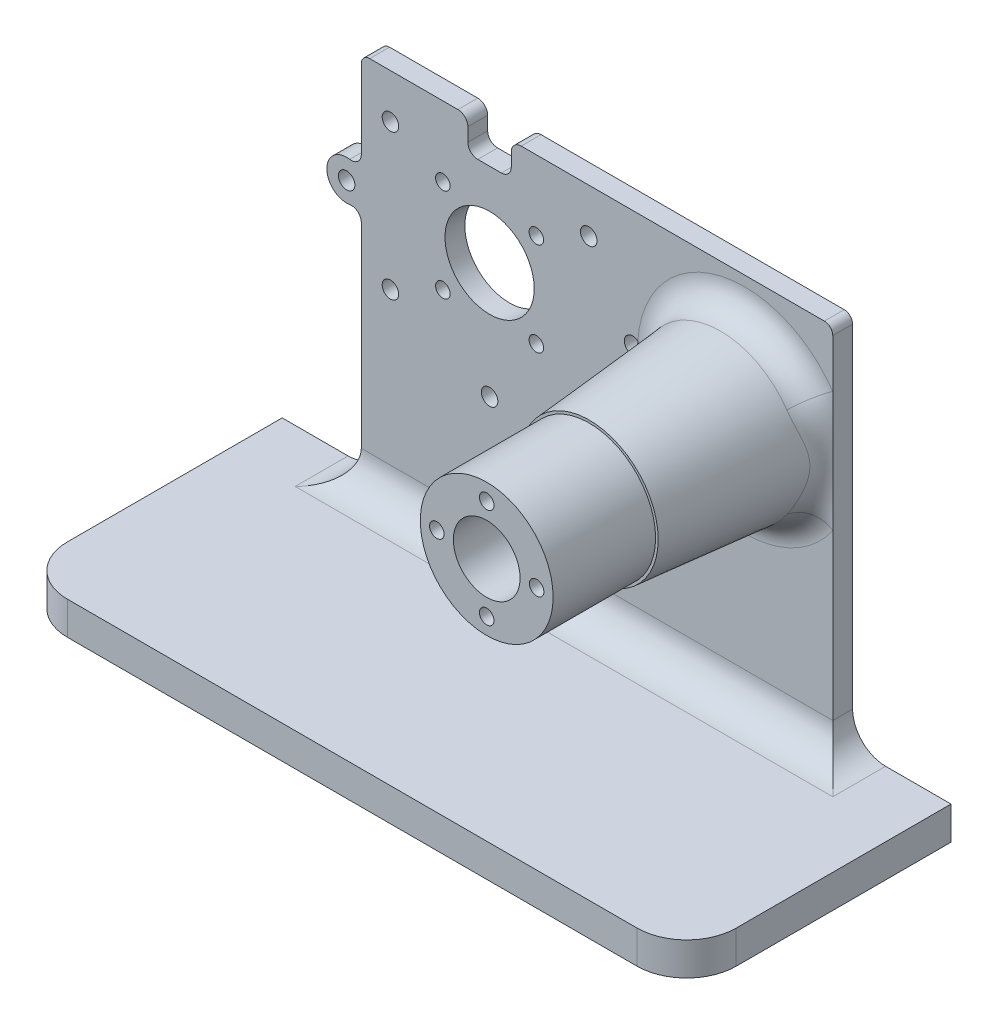
SolidWorks part; units mm, degrees
ref_plane "Front Plane" through (0, 0, 0) normal (0, 0, 1) x (1, 0, 0)
ref_plane "Top Plane" through (0, 0, 0) normal (0, 1, 0) x (1, 0, 0)
ref_plane "Right Plane" through (0, 0, 0) normal (1, 0, 0) x (0, 0, -1)
sketch "Sketch1" plane through (0, 0, 0) normal (0, 0, 1) x (1, 0, 0)
  line L1 (-36.2849, 35.3895) -> (-9.5777, 35.3895)
  line L2 (-38.8249, 32.8495) -> (-38.8249, 8.9302)
  line L3 (-38.8249, -78) -> (103.8382, -78)
  line L4 (103.8382, 32.8495) -> (103.8382, -78)
  line L5 (-38.8249, -8.8387) -> (-38.8249, -78)
  line L6 (0, -55) -> (0, 55) construction
  line L7 (9.5548, 35.3895) -> (101.2982, 35.3895)
  line L9 (-6.5777, 32.3895) -> (-6.5777, 28.3344)
  line L10 (-3.5777, 25.3344) -> (3.5548, 25.3344)
  line L11 (6.5548, 32.3895) -> (6.5548, 28.3344)
  arc A0 (101.2982, 35.3895) -> (103.8382, 32.8495) centre (101.2982, 32.8495) cw
  arc A1 (-36.2849, 35.3895) -> (-38.8249, 32.8495) centre (-36.2849, 32.8495) ccw
  arc A2 (-42.3041, 5.9687) -> (-42.3041, -5.8772) centre (-43.2625, 0.0457) ccw
  circle A3 centre (0, 0) radius 13.5
  circle A4 centre (14.1421, 14.1421) radius 2.2
  circle A5 centre (14.1421, -14.1421) radius 2.2
  arc A6 (-42.3041, -5.8772) -> (-38.8249, -8.8387) centre (-41.8249, -8.8387) cw
  arc A7 (-42.3041, 5.9687) -> (-38.8249, 8.9302) centre (-41.8249, 8.9302) ccw
  circle A8 centre (-14.1421, -14.1421) radius 2.2
  circle A9 centre (-14.1421, 14.1421) radius 2.2
  arc A10 (-6.5777, 28.3344) -> (-3.5777, 25.3344) centre (-3.5777, 28.3344) ccw
  arc A11 (3.5548, 25.3344) -> (6.5548, 28.3344) centre (3.5548, 28.3344) ccw
  arc A12 (9.5548, 35.3895) -> (6.5548, 32.3895) centre (9.5548, 32.3895) ccw
  arc A13 (-9.5777, 35.3895) -> (-6.5777, 32.3895) centre (-9.5777, 32.3895) cw
  dimension "D1" = 2.54
  dimension "D2" = 3
  dimension "D3" = 3
extrude "Boss-Extrude1" add sketch "Sketch1" along normal blind 6 separate body
sketch "Sketch3" plane through (0, 0, 0) normal (0, 0, 1) x (1, 0, 0)
  line L1 (-68.7625, -78) -> (133.625, -78)
  line L2 (-68.7625, -78) -> (-68.7625, -88)
  line L3 (-68.7625, -88) -> (133.625, -88)
  line L4 (133.625, -78) -> (133.625, -88)
extrude "Boss-Extrude2" add sketch "Sketch3" along normal blind 80 separate body
fillet "Fillet1" radius 15 2 edges at (133.625, -83, 80) (-68.7625, -83, 80)
combine bodies "Combine1" operation type add bodies to combine 102 103
fillet "Fillet2" radius 10 3 edges at (103.8382, -78, 3) (-38.8249, -78, 3) (32.5067, -78, 6)
sketch "Sketch4" plane through (0, 0, 6) normal (0, 0, 1) x (1, 0, 0)
  circle A1 centre (77.125, 0) radius 24.9997
extrude "Boss-Extrude3" add sketch "Sketch4" along normal blind 47 draft 5 separate body
combine bodies "Combine2" operation type add bodies to combine 105 104
fillet "Fillet3" radius 8 1 edges at (52.1253, 0, 6)
sketch "Sketch5" plane through (0, 0, 53) normal (0, 0, 1) x (1, 0, 0)
  circle A0 centre (77.125, 0) radius 20.1
  circle A1 centre (77.125, 0) radius 10.1
  circle A2 centre (92.225, 0) radius 2.2
  circle A3 centre (77.125, -15.1) radius 2.2
  circle A4 centre (62.025, 0) radius 2.2
  circle A5 centre (77.125, 15.1) radius 2.2
extrude "Boss-Extrude4" add sketch "Sketch5" along normal blind 31 separate body
sketch "Sketch6" plane through (0, 0, 0) normal (0, 0, 1) x (1, 0, 0)
  circle A0 centre (29.9995, 21.9995) radius 2.5
  circle A1 centre (43.2625, 0) radius 2.5
  circle A2 centre (29.9995, -21.9995) radius 2.5
  circle A3 centre (0, -35.0813) radius 2.5
  circle A4 centre (-29.9995, -21.9995) radius 2.5
  circle A5 centre (-29.9995, 21.9995) radius 2.5
  circle A6 centre (-43.2625, 0) radius 2.5
extrude "Cut-Extrude1" cut sketch "Sketch6" along normal blind 6
fillet "Fillet4" radius 1 7 edges at (-27.4995, -21.9995, 0) (-27.4995, 21.9995, 0) (2.5, -35.0813, 0) (32.4995, -21.9995, 0) (45.7625, 0, 0) (32.4995, 21.9995, 0) (-40.7625, 0, 0)
sketch "Sketch7" plane through (0, 0, 0) normal (0, 0, 1) x (1, 0, 0)
  line L0 (81.125, 15.1) -> (81.125, 9.2742)
  line L1 (73.125, 15.1) -> (73.125, 9.2742)
  line L2 (92.225, 4) -> (86.3992, 4)
  line L3 (92.225, -4) -> (86.3992, -4)
  line L4 (81.125, -15.1) -> (81.125, -9.2742)
  line L5 (73.125, -15.1) -> (73.125, -9.2742)
  line L6 (62.025, -4) -> (67.8508, -4)
  line L7 (62.025, 4) -> (67.8508, 4)
  circle A0 centre (62.025, 0) radius 2.2
  circle A1 centre (77.125, -15.1) radius 2.2
  circle A2 centre (92.225, 0) radius 2.2
  circle A3 centre (77.125, 15.1) radius 2.2
  arc A4 (81.125, 15.1) -> (73.125, 15.1) centre (77.125, 15.1) ccw
  arc A5 (73.125, 9.2742) -> (67.8508, 4) centre (77.125, 0) ccw
  arc A6 (92.225, -4) -> (92.225, 4) centre (92.225, 0) ccw
  arc A7 (73.125, -15.1) -> (81.125, -15.1) centre (77.125, -15.1) ccw
  arc A8 (62.025, 4) -> (62.025, -4) centre (62.025, 0) ccw
  arc A9 (86.3992, 4) -> (81.125, 9.2742) centre (77.125, 0) ccw
  arc A10 (81.125, -9.2742) -> (86.3992, -4) centre (77.125, 0) ccw
  arc A11 (67.8508, -4) -> (73.125, -9.2742) centre (77.125, 0) ccw
  dimension "D1" = 4
extrude "Cut-Extrude2" cut sketch "Sketch7" along normal blind 26
extrude "Cut-Extrude3" cut sketch "Sketch7<2>" along normal blind 83 contours A2 | A3 | A1 | A0 region at (62.025, 0, 0) region at (77.125, -15.1, 0) region at (92.225, 0, 0) region at (77.125, 15.1, 0)
sketch "Sketch7<2>" plane through (0, 0, 0) normal (0, 0, 1) x (1, 0, 0) same geometry as "Sketch7"
sketch "Sketch8" plane through (0, 0, 26) normal (0, 0, -1) x (-1, 0, 0)
  circle A0 centre (-77.125, 0) radius 10.1
extrude "Cut-Extrude4" cut sketch "Sketch8" against normal blind 83
